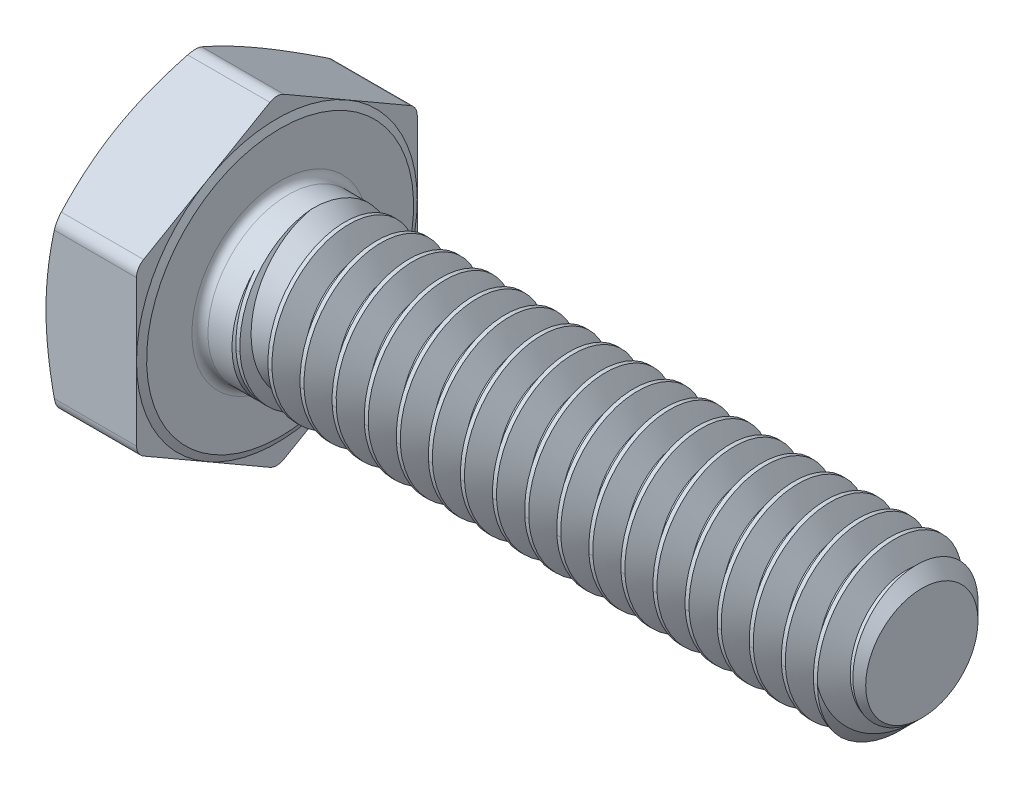
SolidWorks part; units mm, degrees
ref_plane "Front Plane" through (0, 0, 0) normal (0, 0, 1) x (1, 0, 0)
ref_plane "Top Plane" through (0, 0, 0) normal (0, 1, 0) x (1, 0, 0)
ref_plane "Right Plane" through (0, 0, 0) normal (1, 0, 0) x (0, 0, -1)
sketch "Sketch1" plane through (0, 0, 0) normal (0, 0, 1) x (1, 0, 0)
  line L0 (0, 0) -> (25.4, 0) construction
  line L1 (0, 0) -> (-3.9688, 0) construction
  line L2 (0, 5.5562) -> (0, -5.5562) construction
  line L3 (-3.9688, 5.5562) -> (-3.9687, -5.5563) construction
  line L4 (25.4, 3.175) -> (25.4, -3.175) construction
  line L8 (24.13, 3.175) -> (25.4, 3.175) construction
  point P8 (24.13, 0)
  point P11 (20.955, -3.175)
  point P12 (1.27, 0)
  dimension "Head Height" = 3.9688
  dimension "Head Width" = 11.1125
  dimension "Length" = 25.4
  dimension "Thread Size" = 6.35
  dimension "D1" = 4.445
  dimension "Thread Pitch" = 1.27
  dimension "D2" = 1.27
sketch "Sketch2" plane through (0, 0, 0) normal (1, 0, 0) x (0, 0, -1)
  circle A0 centre (0, 0) radius 3.175
extrude "Boss-Extrude1" add sketch "Sketch2" along normal up to vertex (25.4 mm away) up to point (25.4, 3.175, 0)
sketch "Sketch3" plane through (0, 0, 0) normal (-1, 0, 0) x (0, 0, 1)
  line L0 (0, 6.4158) -> (0, 0) construction
  line L1 (0, 6.4158) -> (-5.5563, 3.2079)
  line L2 (-5.5563, 3.2079) -> (-5.5563, -3.2079)
  line L3 (-5.5563, -3.2079) -> (0, -6.4158)
  line L4 (0, -6.4158) -> (5.5562, -3.2079)
  line L5 (5.5562, -3.2079) -> (5.5562, 3.2079)
  line L6 (5.5562, 3.2079) -> (0, 6.4158)
  circle A0 centre (0, 0) radius 5.5562 construction
extrude "Boss-Extrude2" add sketch "Sketch3" along normal up to vertex (3.9688 mm away) up to point (-3.9688, 5.5562, 0)
sketch "Sketch5" plane through (-3.9688, 0, 0) normal (-1, 0, 0) x (0, 0, 1)
  circle A0 centre (0, 0) radius 5.5562 construction
  circle A1 centre (0, 0) radius 5.5562 construction
  circle A2 centre (0, 0) radius 5.0006
  dimension "D1" = 0.5556
extrude "Cut-Extrude1" cut sketch "Sketch5" against normal up to vertex (3.9688 mm away) draft 65 flip side to cut up to point (0, 0, 0)
sketch "Sketch11" plane through (-3.9688, 0, 0) normal (-1, 0, 0) x (0, 0, 1)
  line L0 (0, 3.9449) -> (0, 2.4448) construction
  line L1 (0.2223, 3.9449) -> (0.2223, 2.4448)
  line L2 (-0.2222, 3.9449) -> (-0.2222, 2.4448)
  arc A0 (0.2223, 3.9449) -> (-0.2222, 3.9449) centre (0, 3.9449) ccw
  arc A1 (-0.2222, 2.4448) -> (0.2223, 2.4448) centre (0, 2.4448) ccw
  circle A2 centre (0, 0) radius 4.1672 construction
  circle A3 centre (0, 0) radius 2.2225 construction
  point P3 (0, 3.1948)
  dimension "D1" = 8.3344
  dimension "D2" = 4.445
  dimension "D3" = 0.4445
extrude "Boss-Extrude5" add sketch "Sketch11" along normal blind 0.0635
fillet "Fillet5" radius 0.0635 4 edges at (-4.0323, 3.1948, 0.2223) (-4.0323, 2.2225, 0) (-4.0323, 3.1948, -0.2222) (-4.0323, 4.1672, 0)
fillet "Fillet6" radius 0.0635 4 edges at (-3.9688, 2.2225, 0) (-3.9688, 3.1948, -0.2222) (-3.9688, 4.1672, 0) (-3.9688, 3.1948, 0.2223)
pattern_circular "CirPattern1" count 6 over 360 about axis through (0, 0, 0) along (-1, 0, 0) of "Boss-Extrude5", "Fillet5", "Fillet6" reverse direction yes
fillet "Fillet7" radius 0.5556 6 edges at (-1.6544, -6.4158, 0) (-1.6544, -3.2079, -5.5563) (-1.6544, 3.2079, -5.5563) (-1.6544, 6.4158, 0) (-1.6544, -3.2079, 5.5562) (-1.6544, 3.2079, 5.5562)
chamfer "Chamfer1" distance 0.9525 angle 45 1 edges at (25.4, 0, -3.175)
sketch "Sketch15" plane through (0, 0, 0) normal (0, 0, 1) x (1, 0, 0)
  line L0 (0, 5.2839) -> (-0.127, 5.5562)
  line L1 (0, 5.5562) -> (0, -5.5562) construction
  line L2 (-0.127, 5.5562) -> (-0.127, 6.4158)
  line L3 (-0.127, 6.4158) -> (0, 6.4158)
  line L4 (0, 6.4158) -> (0, 5.2839)
  dimension "D1" = 0.127
  dimension "D2" = 25
revolve "Cut-Revolve1" cut sketch "Sketch15" angle 360 about L1
fillet "Fillet4" radius 0.3175 1 edges at (0, 0, 3.175)
sketch "Reference Sketch1" plane through (0, 0, 0) normal (1, 0, 0) x (0, 0, -1)
  line L1 (0, 6.4158) -> (-5.5563, 3.2079)
  line L2 (-5.5563, 3.2079) -> (-5.5563, -3.2079)
  line L3 (-5.5563, -3.2079) -> (0, -6.4158)
  line L4 (0, -6.4158) -> (5.5563, -3.2079)
  line L5 (5.5563, -3.2079) -> (5.5563, 3.2079)
  line L6 (5.5563, 3.2079) -> (0, 6.4158)
  circle A0 centre (0, 0) radius 5.5563 construction
  circle A1 centre (0, 0) radius 5.5562
sketch "Sketch12" plane through (25.4, 0, 0) normal (1, 0, 0) x (0, 0, -1)
  circle A1 centre (0, 0) radius 3.175
ref_plane "Plane2" through (1.27, 0, 0) normal (1, 0, 0) x (0, 0, -1)
split "Split1" trim tools "Plane2" bodies to split 126 116 resulting bodies 118 119
curve "Helix/Spiral2" pitch 1.27 height 26.67 radius 3.175 centre (25.4, 0, 0) axis (-1, 0, 0) start towards (0, 1, 0) parameters "Pitch"=1.27
sketch "Sketch13" plane through (0, 0, 0) normal (0, 0, 1) x (1, 0, 0)
  line L0 (25.3206, 3.3125) -> (25.9556, 2.2126) construction
  line L1 (25.9556, 2.2126) -> (26.5906, 3.3125) construction
  line L2 (26.5906, 3.3125) -> (25.3206, 3.3125) construction
  line L3 (25.9556, 2.2126) -> (25.9556, 2.3501) construction
  line L4 (25.4, 3.175) -> (26.5113, 3.175)
  line L5 (25.9556, 3.175) -> (25.9556, 3.3125) construction
  line L6 (26.5113, 3.175) -> (26.035, 2.3501)
  line L7 (26.035, 2.3501) -> (25.8762, 2.3501)
  line L8 (25.8762, 2.3501) -> (25.4, 3.175)
  line L9 (24.13, 3.175) -> (25.4, 3.175) construction
  dimension "D1" = 0.1588
sweep "Cut-Sweep1" cut profiles "Sketch13" path "Helix/Spiral2" align with end faces yes
sketch "Sketch14" plane through (1.27, 0, 0) normal (1, 0, 0) x (0, 0, -1)
  circle A1 centre (0, 0) radius 3.175
  circle A2 centre (0, 0) radius 3.175
  dimension "D1" = 0
extrude "Boss-Extrude4" add sketch "Sketch14" along normal through all draft 31.8
equation "\"D1@Sketch11\"=\"Head Width@Sketch1\" * 0.75"
equation "\"D2@Sketch11\"=\"Head Width@Sketch1\"*0.4"
equation "\"D3@Sketch11\"=\"Head Width@Sketch1\" * .04"
equation "\"D3@Helix/Spiral2\"=\"Length@Sketch1\" + \"Thread Pitch@Sketch1\""
equation "\"D1@Chamfer1\"=\"Thread Pitch@Sketch1\"*0.750"
equation "\"D1@Sketch1\"=\"Thread Pitch@Sketch1\"*3.5"
equation "\"Pitch@Helix/Spiral2\"=\"Thread Pitch@Sketch1\""
equation "\"D1@Sketch13\"=\"Thread Pitch@Sketch1\"*0.125"
equation "\"D1@Sketch5\"=\"Head Width@Sketch1\"*0.05"
equation "\"D1@Fillet4\"=\"Thread Size@Sketch1\"*0.05"
equation "\"D2@Sketch1\"=\"Thread Pitch@Sketch1\""
equation "\"D1@Fillet7\"=\"Head Width@Sketch1\"*0.05"
